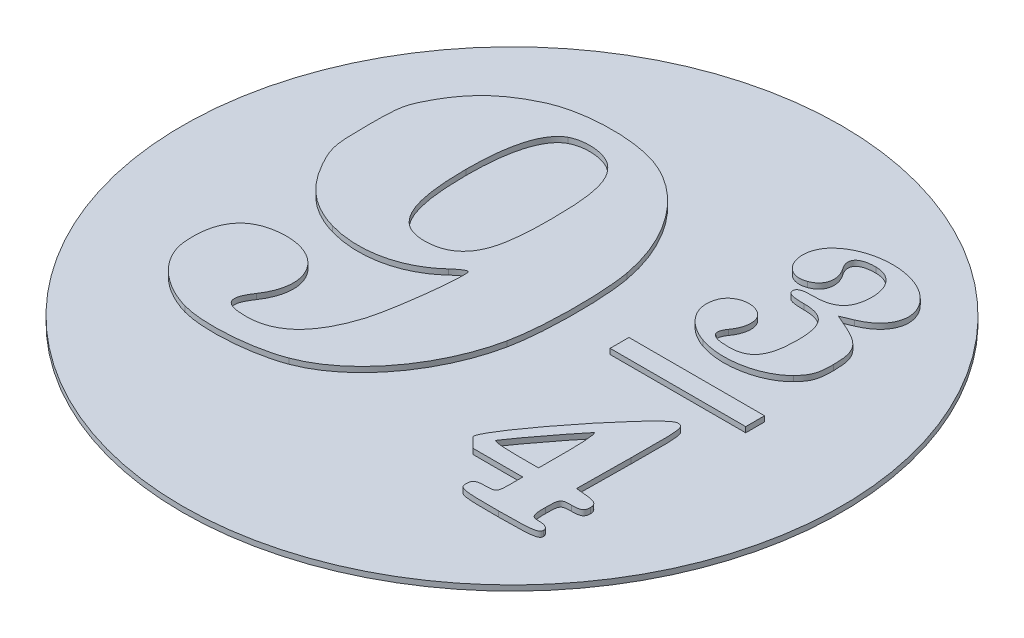
SolidWorks part; units mm, degrees
ref_plane "前视基准面" through (0, 0, 0) normal (0, 0, 1) x (1, 0, 0)
ref_plane "上视基准面" through (0, 0, 0) normal (0, 1, 0) x (1, 0, 0)
ref_plane "右视基准面" through (0, 0, 0) normal (1, 0, 0) x (0, 0, -1)
other "Configuration Table"
sketch "草图1" plane through (0, 0, 0) normal (0, 1, 0) x (1, 0, 0)
  circle A15 centre (0, 0) radius 24.5
  dimension "D1" = 49
extrude "凸台-拉伸3" add sketch "草图1" along normal blind 0.4
sketch "草图10" plane through (0, 0.4, 0) normal (0, 1, 0) x (1, 0, 0)
  line L0 (11.1751, -11.3536) -> (11.1751, -10.3736)
  line L1 (11.1751, -10.3736) -> (7.4816, -10.3736)
  line L2 (7.4816, -10.3736) -> (6.7076, -9.6036)
  line L3 (13.9572, -5.1236) -> (13.913, -9.1136)
  line L4 (13.913, -9.1136) -> (14.784, -9.2014)
  line L5 (9.4951, -9.2009) -> (11.1751, -9.2009)
  line L6 (11.1751, -9.2009) -> (11.1751, -6.9049)
  line L7 (6.1351, 1.8591) -> (6.1351, 2.5591)
  line L8 (6.1351, 2.5591) -> (11.1751, 2.5591)
  line L9 (11.1751, 2.5591) -> (16.2151, 2.5591)
  line L10 (16.2151, 2.5591) -> (16.2151, 1.8591)
  line L11 (16.2151, 1.8591) -> (16.2151, 1.1591)
  line L12 (16.2151, 1.1591) -> (11.1751, 1.1591)
  line L13 (11.1751, 1.1591) -> (6.1351, 1.1591)
  line L14 (6.1351, 1.1591) -> (6.1351, 1.8591)
  line L15 (13.3822, 12.0654) -> (12.5498, 11.7206)
  line L16 (12.5498, 11.7206) -> (13.6124, 11.2442)
  spline S0 degree 3 poles (9.4951, -12.8936) (9.4951, -12.4581) (9.6818, -12.3336) (10.3351, -12.3336) knots 0 0 0 0 1 1 1 1
  spline S1 degree 3 poles (10.3351, -12.3336) (11.1084, -12.3336) (11.1751, -12.2558) (11.1751, -11.3536) knots 0 0 0 0 1 1 1 1
  spline S2 degree 3 poles (6.7076, -9.6036) (6.7247, -8.5573) (12.6255, -1.1336) (13.4401, -1.1336) knots 0 0 0 0 1 1 1 1
  spline S3 degree 3 poles (13.4401, -1.1336) (13.9776, -1.1336) (13.9995, -1.3025) (13.9572, -5.1236) knots 0 0 0 0 1 1 1 1
  spline S4 degree 3 poles (14.784, -9.2014) (15.4287, -9.2663) (15.6551, -9.43) (15.6551, -9.8314) knots 0 0 0 0 1 1 1 1
  spline S5 degree 3 poles (15.6551, -9.8314) (15.6551, -10.2472) (15.4593, -10.3736) (14.8151, -10.3736) knots 0 0 0 0 1 1 1 1
  spline S6 degree 3 poles (14.8151, -10.3736) (14.0218, -10.3736) (13.9751, -10.4358) (13.9751, -11.4936) knots 0 0 0 0 1 1 1 1
  spline S7 degree 3 poles (13.9751, -11.4936) (13.9751, -12.5016) (14.0451, -12.6136) (14.6751, -12.6136) knots 0 0 0 0 1 1 1 1
  spline S8 degree 3 poles (14.6751, -12.6136) (15.1106, -12.6136) (15.3751, -12.7723) (15.3751, -13.0336) knots 0 0 0 0 1 1 1 1
  spline S9 degree 3 poles (15.3751, -13.0336) (15.3751, -13.3803) (14.8618, -13.4536) (12.4351, -13.4536) knots 0 0 0 0 1 1 1 1
  spline S10 degree 3 poles (12.4351, -13.4536) (9.6818, -13.4536) (9.4951, -13.4181) (9.4951, -12.8936) knots 0 0 0 0 1 1 1 1
  spline S11 degree 3 poles (11.1751, -6.9049) (11.1751, -5.6421) (11.0717, -4.7286) (10.9453, -4.8749) knots 0 0 0 0 1 1 1 1
  spline S12 degree 3 poles (10.9453, -4.8749) (10.1204, -5.8299) (7.8151, -8.8905) (7.8151, -9.0306) knots 0 0 0 0 1 1 1 1
  spline S13 degree 3 poles (7.8151, -9.0306) (7.8151, -9.1243) (8.5711, -9.2009) (9.4951, -9.2009) knots 0 0 0 0 1 1 1 1
  spline S14 degree 3 poles (-12.3952, -11.9089) (-14.6847, -11.26) (-16.3951, -9.5677) (-16.5468, -7.8009) knots 0 0 0 0 1 1 1 1
  spline S15 degree 3 poles (-16.5468, -7.8009) (-16.7597, -5.3213) (-15.7908, -3.9165) (-13.7055, -3.6815) knots 0 0 0 0 1 1 1 1
  spline S16 degree 3 poles (-13.7055, -3.6815) (-10.5072, -3.321) (-8.8054, -5.8906) (-10.5459, -8.452) knots 0 0 0 0 1 1 1 1
  spline S17 degree 3 poles (-10.5459, -8.452) (-11.4486, -9.7804) (-11.1284, -10.3214) (-9.4406, -10.3199) knots 0 0 0 0 1 1 1 1
  spline S18 degree 3 poles (-9.4406, -10.3199) (-7.2943, -10.3179) (-5.8007, -8.8893) (-4.9047, -5.9809) knots 0 0 0 0 1 1 1 1
  spline S19 degree 3 poles (-4.9047, -5.9809) (-4.435, -4.4565) (-3.8216, 0.5691) (-4.0743, 0.8218) knots 0 0 0 0 1 1 1 1
  spline S20 degree 3 poles (-4.0743, 0.8218) (-4.1604, 0.9078) (-4.5759, 0.6553) (-4.9978, 0.2606) knots 0 0 0 0 1 1 1 1
  spline S21 degree 3 poles (-4.9978, 0.2606) (-6.8052, -1.4303) (-9.5234, -2.0146) (-12.0892, -1.2637) knots 0 0 0 0 1 1 1 1
  spline S22 degree 3 poles (-12.0892, -1.2637) (-14.0128, -0.7008) (-15.3618, 0.4177) (-16.411, 2.3195) knots 0 0 0 0 1 1 1 1
  spline S23 degree 3 poles (-16.411, 2.3195) (-17.1629, 3.6826) (-17.2385, 4.061) (-17.2415, 6.4791) knots 0 0 0 0 1 1 1 1
  spline S24 degree 3 poles (-17.2415, 6.4791) (-17.2446, 8.9035) (-17.1719, 9.2709) (-16.4199, 10.6283) knots 0 0 0 0 1 1 1 1
  spline S25 degree 3 poles (-16.4199, 10.6283) (-15.41, 12.4515) (-14.1192, 13.6185) (-12.0777, 14.5541) knots 0 0 0 0 1 1 1 1
  spline S26 degree 3 poles (-12.0777, 14.5541) (-10.0857, 15.4669) (-6.5529, 15.5739) (-4.3032, 14.7893) knots 0 0 0 0 1 1 1 1
  spline S27 degree 3 poles (-4.3032, 14.7893) (-1.2608, 13.7283) (1.2079, 10.4902) (1.9116, 6.6376) knots 0 0 0 0 1 1 1 1
  spline S28 degree 3 poles (1.9116, 6.6376) (2.3293, 4.3506) (2.2838, -0.011) (1.8193, -2.2019) knots 0 0 0 0 1 1 1 1
  spline S29 degree 3 poles (1.8193, -2.2019) (0.9187, -6.4498) (-1.9261, -10.1925) (-5.1777, -11.4075) knots 0 0 0 0 1 1 1 1
  spline S30 degree 3 poles (-5.1777, -11.4075) (-7.2474, -12.1809) (-10.6108, -12.4145) (-12.3952, -11.9089) knots 0 0 0 0 1 1 1 1
  spline S31 degree 3 poles (-5.8229, 1.7234) (-4.7498, 2.5676) (-4.3741, 4.0186) (-4.3741, 7.3191) knots 0 0 0 0 1 1 1 1
  spline S32 degree 3 poles (-4.3741, 7.3191) (-4.3741, 10.6195) (-4.7498, 12.0705) (-5.8229, 12.9147) knots 0 0 0 0 1 1 1 1
  spline S33 degree 3 poles (-5.8229, 12.9147) (-6.6088, 13.5328) (-8.1303, 13.6564) (-9.0297, 13.1751) knots 0 0 0 0 1 1 1 1
  spline S34 degree 3 poles (-9.0297, 13.1751) (-10.1622, 12.569) (-10.7607, 10.5331) (-10.7514, 7.3191) knots 0 0 0 0 1 1 1 1
  spline S35 degree 3 poles (-10.7514, 7.3191) (-10.7421, 4.1138) (-10.2508, 2.3291) (-9.1692, 1.5715) knots 0 0 0 0 1 1 1 1
  spline S36 degree 3 poles (-9.1692, 1.5715) (-8.3242, 0.9797) (-6.6732, 1.0547) (-5.8229, 1.7234) knots 0 0 0 0 1 1 1 1
  spline S37 degree 3 poles (9.0751, 5.1377) (7.3764, 5.7331) (6.4995, 7.0481) (6.9721, 8.2912) knots 0 0 0 0 1 1 1 1
  spline S38 degree 3 poles (6.9721, 8.2912) (7.2817, 9.1056) (8.36, 9.4567) (9.189, 9.013) knots 0 0 0 0 1 1 1 1
  spline S39 degree 3 poles (9.189, 9.013) (9.8923, 8.6366) (9.9473, 7.6895) (9.3179, 6.7909) knots 0 0 0 0 1 1 1 1
  spline S40 degree 3 poles (9.3179, 6.7909) (8.7686, 6.0067) (9.132, 5.6476) (10.4751, 5.6476) knots 0 0 0 0 1 1 1 1
  spline S41 degree 3 poles (10.4751, 5.6476) (11.9632, 5.6476) (12.5751, 6.519) (12.5751, 8.6383) knots 0 0 0 0 1 1 1 1
  spline S42 degree 3 poles (12.5751, 8.6383) (12.5751, 10.5626) (12.0247, 11.2391) (10.4592, 11.2391) knots 0 0 0 0 1 1 1 1
  spline S43 degree 3 poles (10.4592, 11.2391) (9.54, 11.2391) (9.2151, 11.3487) (9.2151, 11.6591) knots 0 0 0 0 1 1 1 1
  spline S44 degree 3 poles (9.2151, 11.6591) (9.2151, 11.9694) (9.54, 12.0791) (10.4592, 12.0791) knots 0 0 0 0 1 1 1 1
  spline S45 degree 3 poles (10.4592, 12.0791) (11.8959, 12.0791) (12.5751, 12.7531) (12.5751, 14.1791) knots 0 0 0 0 1 1 1 1
  spline S46 degree 3 poles (12.5751, 14.1791) (12.5751, 15.4663) (11.8778, 16.2791) (10.7735, 16.2791) knots 0 0 0 0 1 1 1 1
  spline S47 degree 3 poles (10.7735, 16.2791) (9.535, 16.2791) (9.0919, 15.7395) (9.662, 14.9256) knots 0 0 0 0 1 1 1 1
  spline S48 degree 3 poles (9.662, 14.9256) (10.2807, 14.0423) (10.06, 13.1211) (9.1536, 12.8036) knots 0 0 0 0 1 1 1 1
  spline S49 degree 3 poles (9.1536, 12.8036) (7.4984, 12.2239) (6.5755, 14.5049) (7.9209, 15.8503) knots 0 0 0 0 1 1 1 1
  spline S50 degree 3 poles (7.9209, 15.8503) (9.452, 17.3814) (12.7011, 17.4691) (14.3195, 16.0231) knots 0 0 0 0 1 1 1 1
  spline S51 degree 3 poles (14.3195, 16.0231) (15.803, 14.6976) (15.3751, 12.8909) (13.3822, 12.0654) knots 0 0 0 0 1 1 1 1
  spline S52 degree 3 poles (13.6124, 11.2442) (15.1071, 10.5741) (15.4828, 10.0063) (15.4828, 8.417) knots 0 0 0 0 1 1 1 1
  spline S53 degree 3 poles (15.4828, 8.417) (15.4828, 7.294) (15.3397, 6.8928) (14.7019, 6.227) knots 0 0 0 0 1 1 1 1
  spline S54 degree 3 poles (14.7019, 6.227) (13.5039, 4.9766) (10.9469, 4.4816) (9.0751, 5.1377) knots 0 0 0 0 1 1 1 1
extrude "凸台-拉伸-9-4-3" add sketch "草图10" along normal blind 0.4
